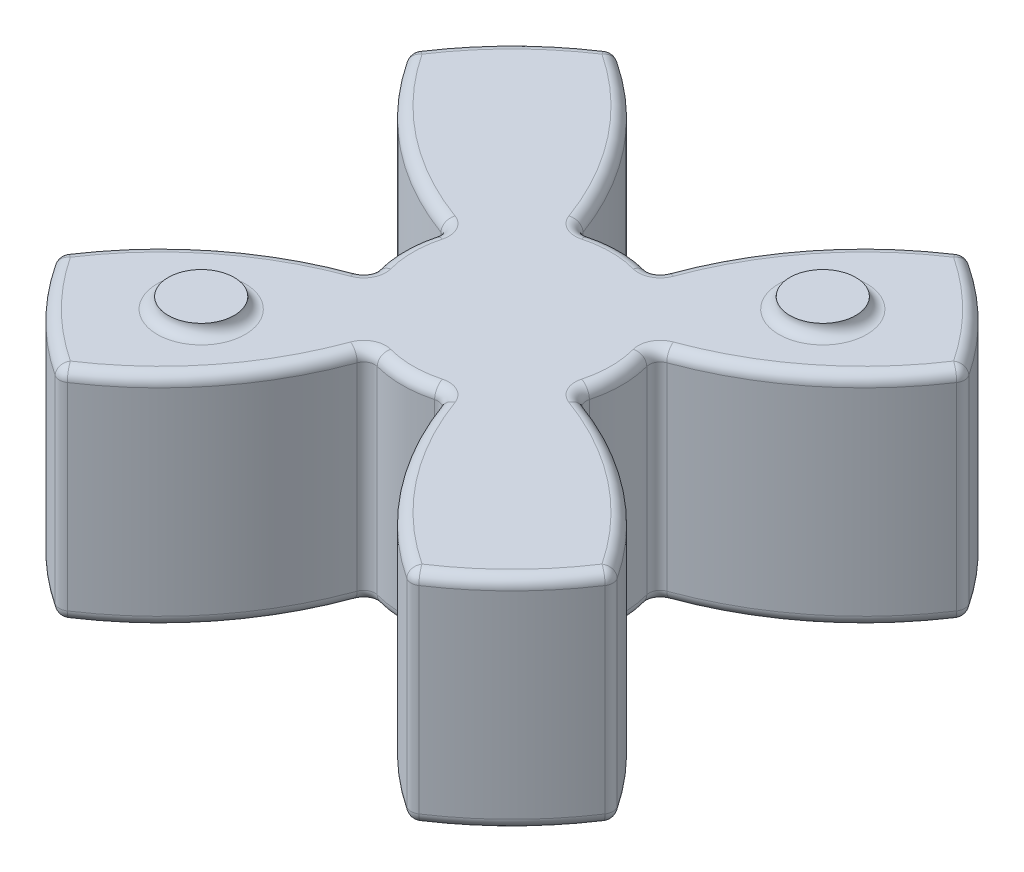
SolidWorks part; units mm, degrees
ref_plane "Front Plane" through (0, 0, 0) normal (0, 0, 1) x (1, 0, 0)
ref_plane "Top Plane" through (0, 0, 0) normal (0, 1, 0) x (1, 0, 0)
ref_plane "Right Plane" through (0, 0, 0) normal (1, 0, 0) x (0, 0, -1)
sketch "Sketch1" plane through (0, 0, 0) normal (0, 1, 0) x (1, 0, 0)
  circle A0 centre (0, 0) radius 15
  dimension "D1" = 30
extrude "Extrude1" add sketch "Sketch1" along normal mid plane 10 contours A0
sketch "Sketch3" plane through (0, -5, 0) normal (0, -1, 0) x (1, 0, 0)
  arc A0 (14.9642, 14.9642) -> (1.75, 4.6837) centre (16, 0) ccw
  arc A1 (14.9642, -14.9642) -> (4.6837, -1.75) centre (0, -16) ccw
  arc A2 (-14.9642, -14.9642) -> (-1.75, -4.6837) centre (-16, 0) ccw
  arc A3 (-14.9642, 14.9642) -> (-4.6837, 1.75) centre (0, 16) ccw
  circle A4 centre (0, 0) radius 5
  arc A5 (1.75, -4.6837) -> (14.9642, -14.9642) centre (16, 0) ccw
  arc A6 (-1.75, 4.6837) -> (-14.9642, 14.9642) centre (-16, 0) ccw
  arc A7 (4.6837, 1.75) -> (14.9642, 14.9642) centre (0, 16) ccw
  arc A8 (-4.6837, -1.75) -> (-14.9642, -14.9642) centre (0, -16) ccw
  point P11 (0, 0)
  circle M1 centre (0, 0) radius 15
  dimension "D1" = 30
  dimension "D4" = 16
  dimension "D5" = 10
  dimension "D2" = 16
  dimension "D3" = 4
extrude "Extrude2" cut sketch "Sketch3" against normal through all flip side to cut contours A4 A7 A0 M1 | A4 A5 A1 M1 | A4 A8 A2 M1 | A4 A6 A3 M1 | A4 region at (7.1526, -5, 7.1526) region at (0, -5, 0) region at (-7.1526, -5, 7.1526) region at (7.1526, -5, -7.1526) region at (-7.1526, -5, -7.1526)
sketch "Sketch4" plane through (0, 5, 0) normal (0, 1, 0) x (1, 0, 0)
  line L0 (-7.0711, -7.0711) -> (7.0711, 7.0711) construction
  line L1 (0, 0) -> (5.6638, 0) construction
  circle A0 centre (7.0711, 7.0711) radius 1.5
  circle A1 centre (-7.0711, -7.0711) radius 1.5
  point P4 (0, 0)
  dimension "D1" = 45
  dimension "D3" = 3
  dimension "D4" = 3
  dimension "D2" = 20
extrude "Extrude3" add sketch "Sketch4" along normal blind 0.5
mirror "Mirror1" about plane through (0, 0, 0) normal (0, 1, 0) of "Extrude3"
fillet "Fillet1" radius 0.5 52 edges at (5, 5, 0) (5, -5, 0) (0, 5, 5) (0, -5, 5) (-5, 5, 0) (-5, -5, 0) (0, 5, -5) (0, -5, -5) (7.0711, 5, -5.5711) (-7.0711, 5, 8.5711) (7.0711, -5, -5.5711) (-7.0711, -5, 8.5711) (4.6837, 0, -1.75) (9.2312, 5, -4.1769) (12.6886, 0, -8) (9.2312, -5, -4.1769) (12.6886, 0, 8) (9.2312, 5, 4.1769) (4.6837, 0, 1.75) (9.2312, -5, 4.1769) (1.75, 0, 4.6837) (4.1769, 5, 9.2312) (8, 0, 12.6886) (4.1769, -5, 9.2312) (-8, 0, 12.6886) (-4.1769, 5, 9.2312) (-1.75, 0, 4.6837) (-4.1769, -5, 9.2312) (-4.6837, 0, 1.75) (-9.2312, 5, 4.1769) (-12.6886, 0, 8) (-9.2312, -5, 4.1769) (-12.6886, 0, -8) (-9.2312, 5, -4.1769) (-4.6837, 0, -1.75) (-9.2312, -5, -4.1769) (-1.75, 0, -4.6837) (-4.1769, 5, -9.2312) (-8, 0, -12.6886) (-4.1769, -5, -9.2312) (8, 0, -12.6886) (4.1769, 5, -9.2312) (1.75, 0, -4.6837) (4.1769, -5, -9.2312) (10.6066, -5, -10.6066) (-10.6066, -5, -10.6066) (-10.6066, -5, 10.6066) (10.6066, -5, 10.6066) (-10.6066, 5, 10.6066) (-10.6066, 5, -10.6066) (10.6066, 5, -10.6066) (10.6066, 5, 10.6066)
